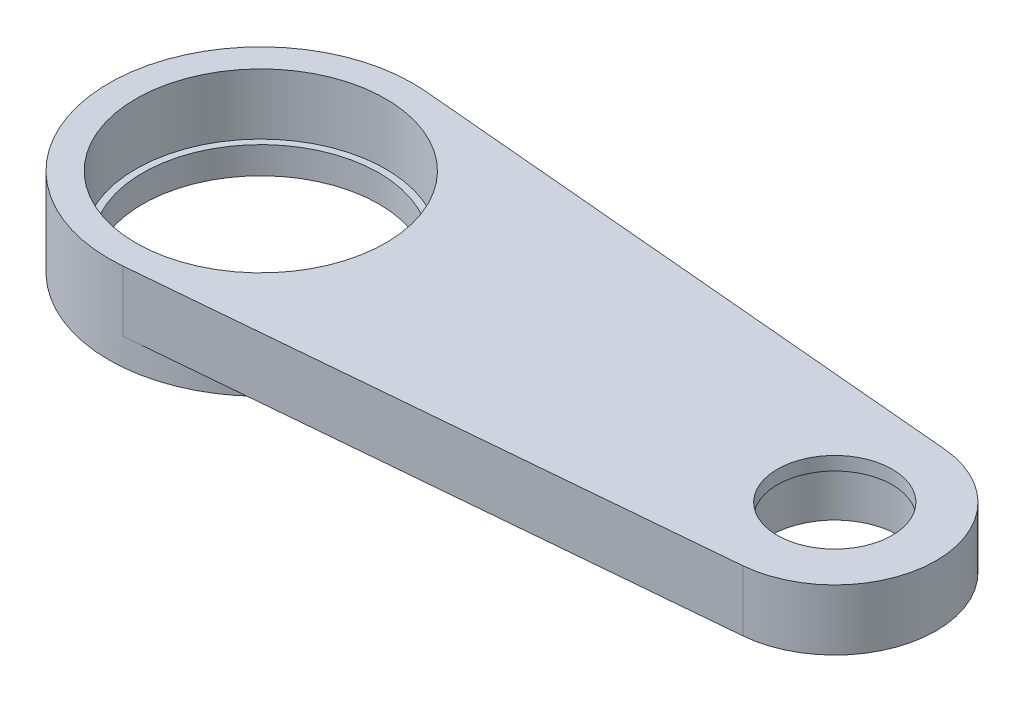
SolidWorks part; units mm, degrees
other "마크업1"
sketch "스케치8" plane through (80, 10, 22.5) normal (0.0741, 0.9433, 0.3234) x (0.9972, -0.0727, -0.0163)
sketch "스케치15" plane through (100, 13, 22.5) normal (0.0741, 0.9433, 0.3234) x (0.9972, -0.0727, -0.0163)
material "7075-T6 (SN)"
ref_plane "정면" through (0, 0, 0) normal (0, 0, 1) x (1, 0, 0)
ref_plane "윗면" through (0, 0, 0) normal (0, 1, 0) x (1, 0, 0)
ref_plane "우측면" through (0, 0, 0) normal (1, 0, 0) x (0, 0, -1)
sketch "스케치1" plane through (0, 0, 0) normal (0, 1, 0) x (1, 0, 0)
  circle A0 centre (0, 0) radius 17.5
  circle A1 centre (0, 0) radius 22.5
  dimension "D1" = 35
  dimension "D2" = 45
extrude "보스-돌출1" add sketch "스케치1" along normal blind 8 contours A1 | A0
sketch "스케치2" plane through (0, 8, 0) normal (0, 1, 0) x (1, 0, 0)
  circle A0 centre (0, 0) radius 18.5
  circle A1 centre (0, 0) radius 22.5 construction
  circle A2 centre (0, 0) radius 22.5
  dimension "D1" = 37
extrude "보스-돌출2" add sketch "스케치2" along normal blind 5
sketch "스케치3" plane through (0, 13, 0) normal (0, 1, 0) x (1, 0, 0)
  line L0 (1.9853, 22.4122) -> (86.3235, 14.9415)
  line L1 (0, 0) -> (85, 0) construction
  line L2 (1.9853, -22.4122) -> (86.3235, -14.9415)
  circle A0 centre (0, 0) radius 22.5 construction
  arc A1 (1.9853, -22.4122) -> (1.9853, 22.4122) centre (0, 0) ccw
  arc A2 (86.3235, -14.9415) -> (86.3235, 14.9415) centre (85, 0) ccw
  dimension "D2" = 30
  dimension "D1" = 85
extrude "보스-돌출3" add sketch "스케치3" against normal blind 9
sketch "스케치7" plane through (0, 8, 0) normal (0, 1, 0) x (1, 0, 0)
  circle A0 centre (0, 0) radius 18.5 construction
  circle A1 centre (0, 0) radius 18.5
extrude "컷-돌출4" cut sketch "스케치7" against normal blind 4
sketch "스케치13" plane through (0, 4, 0) normal (0, -1, 0) x (1, 0, 0)
  circle A0 centre (85, 0) radius 9.5
  dimension "D1" = 19
extrude "컷-돌출9" cut sketch "스케치13" against normal blind 7
sketch "스케치14" plane through (0, 11, 0) normal (0, -1, 0) x (1, 0, 0)
  circle A0 centre (85, 0) radius 8.5
  dimension "D1" = 17
extrude "컷-돌출10" cut sketch "스케치14" against normal through all
